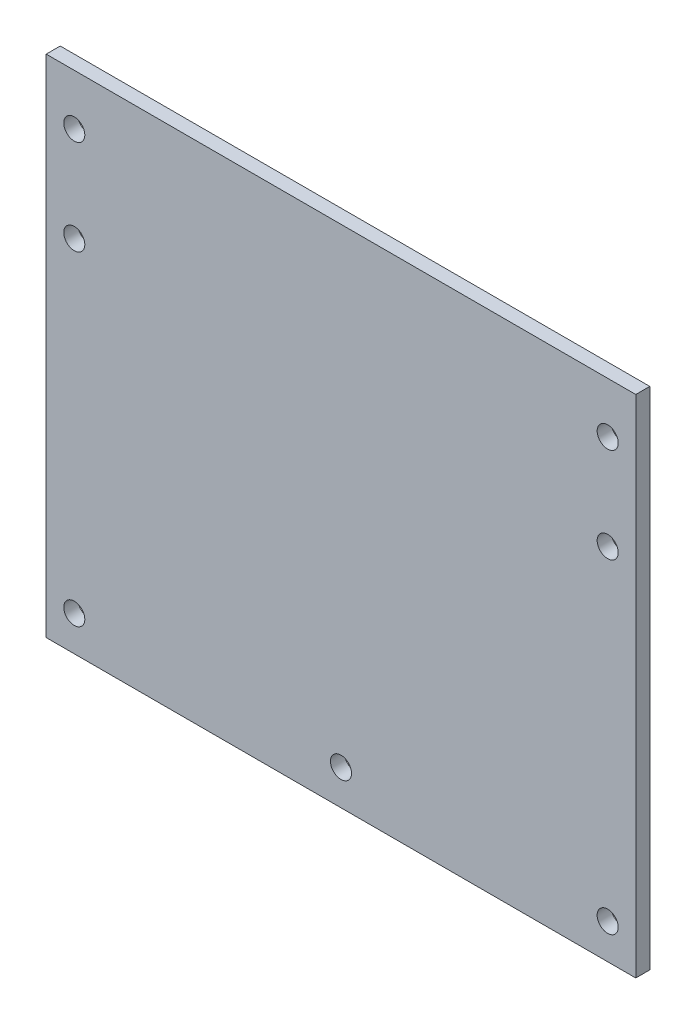
SolidWorks part; units mm, degrees
ref_plane "Front Plane" through (0, 0, 0) normal (0, 0, 1) x (1, 0, 0)
ref_plane "Top Plane" through (0, 0, 0) normal (0, 1, 0) x (1, 0, 0)
ref_plane "Right Plane" through (0, 0, 0) normal (1, 0, 0) x (0, 0, -1)
sketch "Sketch1" plane through (0, 0, 0) normal (0, 0, 1) x (1, 0, 0)
  line L1 (0, 0) -> (533.4, 0)
  line L2 (0, 0) -> (0, -457.2)
  line L3 (0, -457.2) -> (533.4, -457.2)
  line L4 (533.4, 0) -> (533.4, -457.2)
  dimension "D1" = 533.4
  dimension "D2" = 457.2
extrude "Boss-Extrude1" add sketch "Sketch1" along normal blind 12.7
sketch "Sketch3" plane through (0, 0, 0) normal (0, 0, -1) x (-1, 0, 0)
  line L0 (-533.4, -45.974) -> (-508, -45.974) construction
  line L1 (-533.4, -457.2) -> (-533.4, 0) construction
  line L2 (-508, -45.974) -> (-508, -527.4873) construction
  line L3 (-266.7, 0) -> (-266.7, -457.2) construction
  line L4 (-533.4, 0) -> (0, 0) construction
  line L5 (0, -457.2) -> (-533.4, -457.2) construction
  line L6 (-508, -45.974) -> (-508, 0)
  line L7 (-533.4, -106.426) -> (-508, -106.426) construction
  line L8 (-533.4, -198.628) -> (-508, -198.628) construction
  line L9 (-533.4, -259.08) -> (-508, -259.08) construction
  line L10 (-533.4, -425.45) -> (0, -425.45) construction
  line L11 (0, 0) -> (0, -457.2) construction
  dimension "D1" = 45.974
  dimension "D2" = 60.452
  dimension "D3" = 92.202
  dimension "D4" = 60.452
  dimension "D5" = 31.75
sketch "Sketch4" plane through (0, 0, 0) normal (0, 0, -1) x (-1, 0, 0)
  line L0 (-266.7, 0) -> (-266.7, -457.2) construction
  line L1 (-266.7, -425.45) -> (38.9719, -425.45) construction
  line L2 (-533.4, -425.45) -> (0, -425.45) construction
  line L3 (0, -457.2) -> (-533.4, -457.2) construction
  line L5 (-508, -45.974) -> (-508, -527.4873) construction
  line L8 (-533.4, -425.45) -> (-508, -425.45) construction
  circle A0 centre (-508, -45.974) radius 9.525
  circle A1 centre (-508, -131.826) radius 9.525
  circle A2 centre (-508, -425.45) radius 9.525
  circle A3 centre (-25.4, -425.45) radius 9.525
  circle A4 centre (-25.4, -131.826) radius 9.525
  circle A7 centre (-25.4, -45.974) radius 9.525
  circle A8 centre (-266.7, -425.45) radius 9.525
  dimension "D1" = 19.05
  dimension "D2" = 19.05
  dimension "D6" = 19.05
  dimension "D5" = 31.75
extrude "Cut-Extrude1" cut sketch "Sketch4" against normal blind 12.7
sketch3d "3DSketch1" plane through (0, 0, 0) normal (0, 0, 1) x (1, 0, 0)
  dimension "D1" = 90
